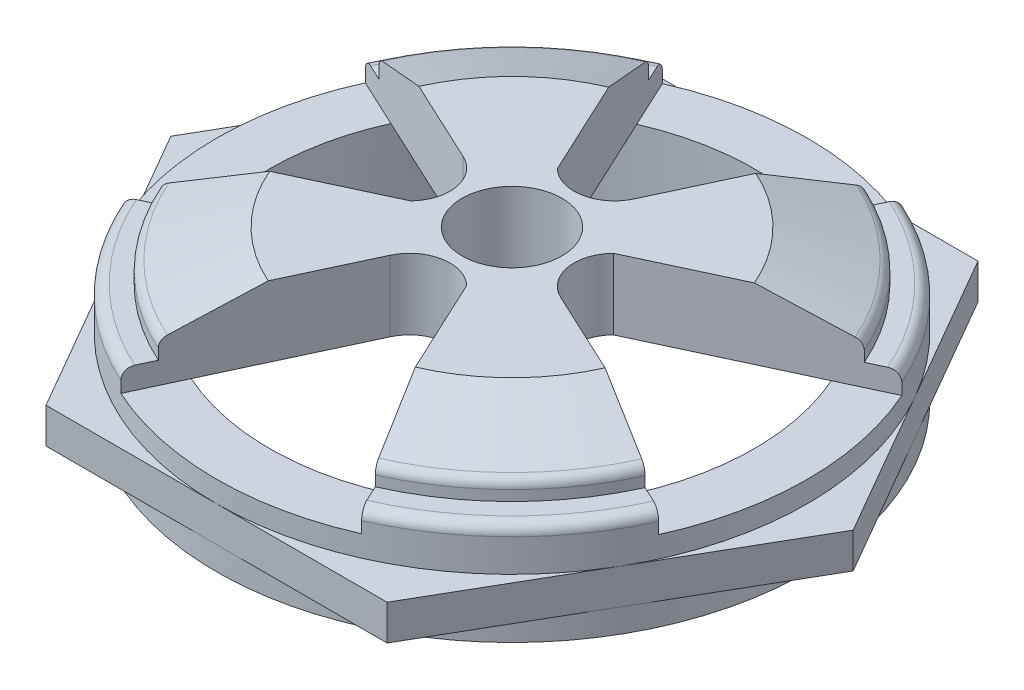
SolidWorks part; units mm, degrees
note: The reader was unsure of these and kept them because the rebuilt part matched: shared geometry of "Sketch2<3>", "Sketch2<4>".
material "2024-O"
ref_plane "Front Plane" through (0, 0, 0) normal (0, 0, 1) x (1, 0, 0)
ref_plane "Top Plane" through (0, 0, 0) normal (0, 1, 0) x (1, 0, 0)
ref_plane "Right Plane" through (0, 0, 0) normal (1, 0, 0) x (0, 0, -1)
sketch "Sketch1" plane through (0, 0, 0) normal (0, 0, 1) x (1, 0, 0)
  line L0 (0, -1000) -> (0, 49000) construction
  line L1 (0, 12.35) -> (0, -12.35)
  line L2 (-20.9, 12.35) -> (20.9, 12.35) construction
  line L3 (-20.9, 12.35) -> (-20.9, -12.35) construction
  line L4 (-20.9, -12.35) -> (20.9, -12.35) construction
  line L5 (20.9, 12.35) -> (20.9, -12.35) construction
  line L6 (-20.9, 12.35) -> (20.9, -12.35) construction
  line L7 (-20.9, -12.35) -> (20.9, 12.35) construction
  line L8 (0, -12.35) -> (-18.9042, -12.35)
  line L9 (-19.6542, -11.6) -> (-19.6542, -11.1)
  line L10 (-19.6542, -11.1) -> (-20.9, -11.1)
  line L11 (-20.9, -11.1) -> (-20.9, 8.15)
  line L12 (-20.15, 8.9) -> (-18.9042, 8.9)
  line L13 (-18.9042, 8.9) -> (-18.9042, 9.6308)
  line L14 (-18.4182, 10.3328) -> (-13.0542, 12.35)
  line L15 (-13.0542, 12.35) -> (0, 12.35)
  arc A0 (-20.9, 8.15) -> (-20.15, 8.9) centre (-20.15, 8.15) cw
  arc A1 (-18.9042, 9.6308) -> (-18.4182, 10.3328) centre (-18.1542, 9.6308) cw
  arc A2 (-18.9042, -12.35) -> (-19.6542, -11.6) centre (-18.9042, -11.6) cw
  point P1 (0, 0)
  point P19 (-20.9, 8.9)
  point P22 (-18.9042, 10.15)
  point P25 (-19.6542, -12.35)
  dimension "D5" = 1.25
  dimension "D7" = 0.75
  dimension "D1" = 24.7
  dimension "D2" = 41.8
  dimension "D3" = 1.25
  dimension "D4" = 20
  dimension "D6" = 6.25
revolve "Revolve1" add sketch "Sketch1" angle 360 about L0
sketch "Sketch2" plane through (0, 12.35, 0) normal (0, 1, 0) x (1, 0, 0)
  line L0 (0, -1000) -> (0, 49000) construction
  line L1 (-8.4703, 19.1067) -> (-1.9787, 5.1854)
  line L2 (2.5917, 6.0415) -> (8.6471, 19.0273)
  line L3 (19.1067, 8.4703) -> (5.1854, 1.9787)
  line L4 (6.0415, -2.5917) -> (19.0273, -8.6471)
  line L5 (8.4703, -19.1067) -> (1.9787, -5.1854)
  line L6 (-2.5917, -6.0415) -> (-8.6471, -19.0273)
  line L7 (-19.1067, -8.4703) -> (-5.1854, -1.9787)
  line L8 (-6.0415, 2.5917) -> (-19.0273, 8.6471)
  line L10 (-2.5, 2.5) -> (2.5, 2.5)
  line L11 (-2.5, 2.5) -> (-2.5, -2.5)
  line L12 (-2.5, -2.5) -> (2.5, -2.5)
  line L13 (2.5, 2.5) -> (2.5, -2.5)
  line L14 (-2.5, 2.5) -> (2.5, -2.5) construction
  line L15 (-2.5, -2.5) -> (2.5, 2.5) construction
  circle A0 centre (0, 0) radius 20.9 construction
  arc A1 (-19.0273, 8.6471) -> (-19.1067, -8.4703) centre (0, 0) ccw
  circle A2 centre (0, 0) radius 17.15
  arc A3 (-1.9787, 5.1854) -> (2.5917, 6.0415) centre (0, 7.25) ccw
  arc A4 (5.1854, 1.9787) -> (6.0415, -2.5917) centre (7.25, 0) ccw
  arc A5 (1.9787, -5.1854) -> (-2.5917, -6.0415) centre (0, -7.25) ccw
  arc A6 (-5.1854, -1.9787) -> (-6.0415, 2.5917) centre (-7.25, 0) ccw
  arc A7 (-8.6471, -19.0273) -> (8.4703, -19.1067) centre (0, 0) ccw
  arc A8 (19.0273, -8.6471) -> (19.1067, 8.4703) centre (0, 0) ccw
  arc A9 (8.6471, 19.0273) -> (-8.4703, 19.1067) centre (0, 0) ccw
  circle A10 centre (0, 0) radius 3.5355
  point P29 (0, 0)
  dimension "D1" = 3.75
  dimension "D4" = 7.25
  dimension "D2" = 25
  dimension "D3" = 25
  dimension "D6" = 5
  dimension "D5" = 4
extrude "Cut-Extrude1" cut sketch "Sketch2" against normal blind 5 contours L8 A1 L7 A6 | L1 A3 L2 A9 | L4 A8 L3 A4 | L6 A7 L5 A5
sketch "Sketch4" plane through (0, -12.35, 0) normal (0, -1, 0) x (1, 0, 0)
  line L0 (0, -999.962) -> (0, 49000.038) construction
  line L1 (19.7505, 6.8356) -> (6.392, 2.3659)
  line L2 (-6.8356, 19.7505) -> (-2.3659, 6.392)
  line L3 (2.3867, 6.4514) -> (6.8364, 19.7503)
  line L4 (6.4514, -2.3867) -> (19.7503, -6.8364)
  line L5 (6.8356, -19.7505) -> (2.3659, -6.392)
  line L6 (-2.3867, -6.4514) -> (-6.8364, -19.7503)
  line L7 (-19.7505, -6.8356) -> (-6.392, -2.3659)
  line L8 (-6.4514, 2.3867) -> (-19.7503, 6.8364)
  arc A0 (8.4703, 19.1067) -> (-8.6471, 19.0273) centre (0, 0) ccw construction
  arc A1 (-2.3659, 6.392) -> (2.3867, 6.4514) centre (0, 7.25) ccw
  arc A2 (6.8364, 19.7503) -> (-6.8356, 19.7505) centre (0, 0) ccw
  arc A3 (6.392, 2.3659) -> (6.4514, -2.3867) centre (7.25, 0) ccw
  arc A4 (19.7503, -6.8364) -> (19.7505, 6.8356) centre (0, 0) ccw
  arc A5 (2.3659, -6.392) -> (-2.3867, -6.4514) centre (0, -7.25) ccw
  arc A6 (-6.8364, -19.7503) -> (6.8356, -19.7505) centre (0, 0) ccw
  arc A7 (-6.392, -2.3659) -> (-6.4514, 2.3867) centre (-7.25, 0) ccw
  arc A8 (-19.7503, 6.8364) -> (-19.7505, -6.8356) centre (0, 0) ccw
  point P30 (0, 0)
  dimension "D3" = 4
  dimension "D1" = 18.5
  dimension "D2" = 18.5
extrude "Cut-Extrude2" cut sketch "Sketch4" against normal blind 2.5 contours L8 A8 L7 A7 | L2 A1 L3 A2 | L1 A3 L4 A4 | L5 A5 L6 A6
extrude "Cut-Extrude3" cut sketch "Sketch2<3>" against normal up to surface (17.2 mm away) from offset 5 contours A2 up to face at (-0.0107, -9.85, -12.9514) offset against normal yes
sketch "Sketch2<3>" plane through (0, 12.35, 0) normal (0, 1, 0) x (1, 0, 0) same geometry as "Sketch2"
extrude "Cut-Extrude4" cut sketch "Sketch2<4>" against normal through all contours A10
sketch "Sketch2<4>" plane through (0, 12.35, 0) normal (0, 1, 0) x (1, 0, 0) same geometry as "Sketch2"
sketch "Sketch5" plane through (0, 7.35, 0) normal (0, 1, 0) x (1, 0, 0)
  line L1 (-12.0666, 20.9) -> (-24.1332, 0)
  line L2 (-24.1332, 0) -> (-12.0666, -20.9)
  line L3 (-12.0666, -20.9) -> (12.0666, -20.9)
  line L4 (12.0666, -20.9) -> (24.1332, 0)
  line L5 (24.1332, 0) -> (12.0666, 20.9)
  line L6 (12.0666, 20.9) -> (-12.0666, 20.9)
  arc A0 (-19.0273, 8.6471) -> (-19.1067, -8.4703) centre (0, 0) ccw construction
  arc A1 (-19.0273, 8.6471) -> (-19.1067, -8.4703) centre (0, 0) ccw
  circle A2 centre (0, 0) radius 20.9 construction
  circle A3 centre (0, 0) radius 18.75
  line M5 (-15.6284, 7.0622) -> (-19.0273, 8.6471)
  arc M6 (-19.0273, 8.6471) -> (-19.1067, -8.4703) centre (0, 0) ccw
  line M7 (-19.1067, -8.4703) -> (-15.7073, -6.8851)
  dimension "D1" = 20.9
  dimension "D2" = 2.15
extrude "Boss-Extrude1" add sketch "Sketch5" against normal blind 2.5 from offset 1.5 contours L5 L6 L1 L2 L3 L4 A3 M7 M6 M5 offset against normal yes
ref_plane "Plane1" through (0, 1.675, 0) normal (0, 1, 0) x (1, 0, 0)
other "SurfaceCut1"
